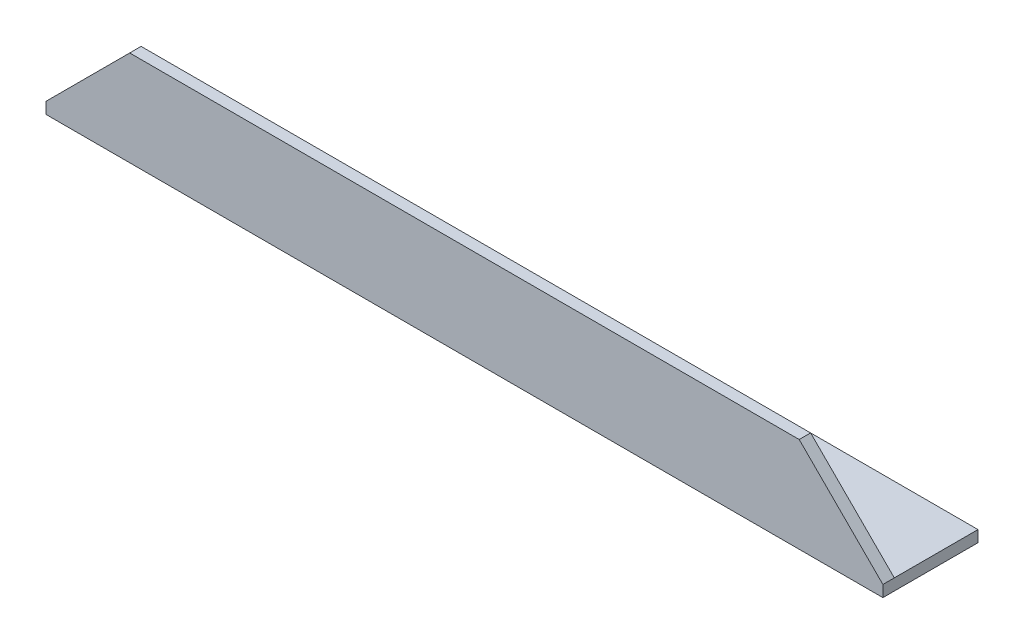
SolidWorks part; units mm, degrees
ref_plane "Спереди" through (0, 0, 0) normal (0, 0, 1) x (1, 0, 0)
ref_plane "Сверху" through (0, 0, 0) normal (0, 1, 0) x (1, 0, 0)
ref_plane "Справа" through (0, 0, 0) normal (1, 0, 0) x (0, 0, -1)
sketch "Эскиз1" plane through (0, 0, 0) normal (1, 0, 0) x (0, 0, -1)
  line L0 (0, 25) -> (0, 0)
  line L1 (0, 0) -> (25, 0)
  line L2 (25, 0) -> (25, 3)
  line L3 (25, 3) -> (3, 3)
  line L4 (3, 3) -> (3, 25)
  line L5 (3, 25) -> (0, 25)
extrude "Бобышка-Вытянуть1" add sketch "Эскиз1" along normal blind 220
sketch "Эскиз2" plane through (0, 0, 0) normal (0, 0, 1) x (1, 0, 0)
  line L0 (0, 0) -> (220, 0)
  line L1 (220, 0) -> (220, 3)
  line L2 (220, 3) -> (198, 25)
  line L3 (220, 25) -> (0, 25) construction
  line L4 (198, 25) -> (22, 25)
  line L5 (22, 25) -> (0, 3)
  line L6 (0, 25) -> (0, 0) construction
  line L7 (0, 3) -> (0, 0)
extrude "Вырез-Вытянуть1" cut sketch "Эскиз2" against normal blind 220 flip side to cut
